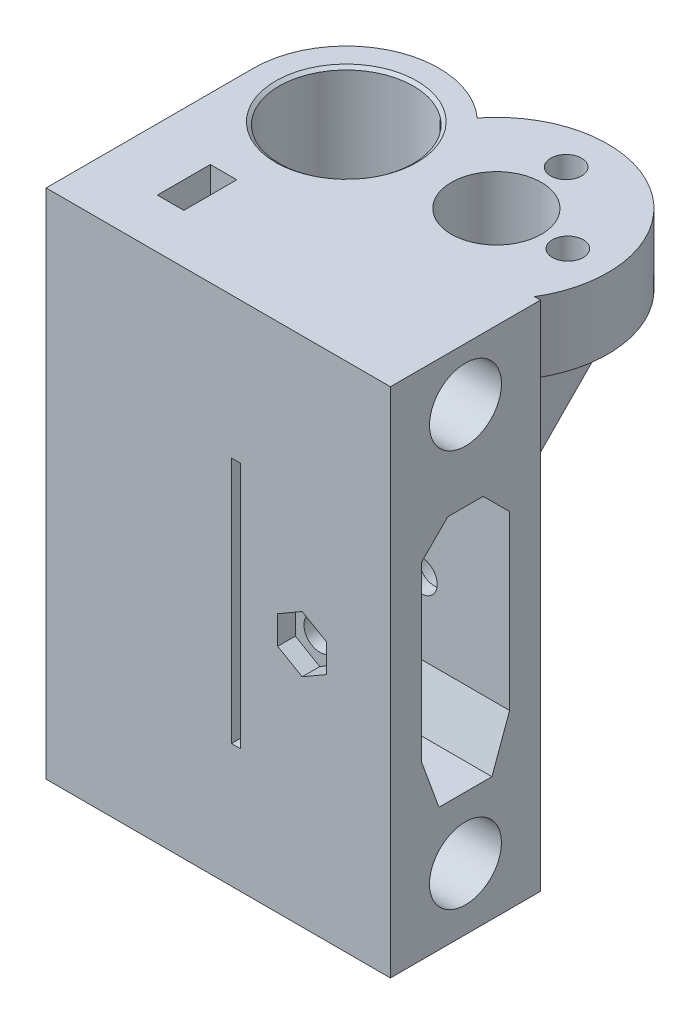
SolidWorks part; units mm, degrees
ref_plane "Front Plane" through (0, 0, 0) normal (0, 0, 1) x (1, 0, 0)
ref_plane "Top Plane" through (0, 0, 0) normal (0, 1, 0) x (1, 0, 0)
ref_plane "Right Plane" through (0, 0, 0) normal (1, 0, 0) x (0, 0, -1)
sketch "Sketch1" plane through (0, 0, 0) normal (0, 0, 1) x (1, 0, 0)
  line L1 (-40.75, -31) -> (40.75, -31)
  line L2 (-40.75, -31) -> (-40.75, 31)
  line L3 (-40.75, 31) -> (40.75, 31)
  line L4 (40.75, -31) -> (40.75, 31)
  line L5 (-40.75, -31) -> (40.75, 31) construction
  line L6 (-40.75, 31) -> (40.75, -31) construction
  point P0 (0, 0)
  dimension "D1" = 81.5
  dimension "D2" = 62
extrude "Boss-Extrude1" add sketch "Sketch1" along normal blind 17
sketch "Sketch2" plane through (0, 0, 17) normal (0, 0, 1) x (1, 0, 0)
  line L0 (22.55, -31) -> (22.55, -27)
  line L1 (-40.75, -31) -> (40.75, -31) construction
  line L2 (22.55, -27) -> (1.75, -27)
  line L3 (1.75, -27) -> (1.75, -22)
  line L4 (1.75, -22) -> (-10.75, -22)
  line L5 (-10.75, -22) -> (-10.75, 11.75)
  line L6 (-10.75, 11.75) -> (-40.75, 11.75)
  line L7 (-40.75, 31) -> (-40.75, -31) construction
  line L8 (-40.75, 11.75) -> (-40.75, -31)
  line L9 (-40.75, -31) -> (22.55, -31)
  line L10 (40.75, -31) -> (40.75, 31) construction
  line L11 (40.75, 31) -> (-40.75, 31) construction
  dimension "D1" = 18.2
  dimension "D2" = 4
  dimension "D3" = 20.8
  dimension "D4" = 5
  dimension "D5" = 12.5
  dimension "D6" = 19.25
extrude "Cut-Extrude2" cut sketch "Sketch2" against normal through all
chamfer "Chamfer2" distance 11 angle 45 1 edges at (-40.75, 31, 8.5)
sketch "Sketch3" plane through (0, 0, 0) normal (0, 0, -1) x (-1, 0, 0)
  line L0 (-40.75, 31) -> (29.75, 31) construction
  line L1 (35.25, -14.75) -> (4.25, -14.75) construction
  line L2 (35.25, -14.75) -> (35.25, 16.25) construction
  line L3 (35.25, 16.25) -> (4.25, 16.25) construction
  line L4 (4.25, -14.75) -> (4.25, 16.25) construction
  line L5 (35.25, -14.75) -> (4.25, 16.25) construction
  line L6 (35.25, 16.25) -> (4.25, -14.75) construction
  line L7 (-40.75, -31) -> (-40.75, 31) construction
  circle A0 centre (35.25, 16.25) radius 1.8
  circle A1 centre (4.25, 16.25) radius 1.8
  circle A2 centre (4.25, -14.75) radius 1.8
  point P0 (19.75, 0.75)
  dimension "D4" = 3.6
  dimension "D1" = 31
  dimension "D2" = 30.25
  dimension "D3" = 60.5
extrude "Cut-Extrude3" cut sketch "Sketch3" against normal through all
sketch "Sketch4" plane through (0, 0, 17) normal (0, 0, 1) x (1, 0, 0)
  circle A0 centre (-4.25, -14.75) radius 3.1
  circle A1 centre (-4.25, 16.25) radius 3.1
  circle A2 centre (-35.25, 16.25) radius 3.1
  dimension "D1" = 6.2
extrude "Cut-Extrude4" cut sketch "Sketch4" against normal blind 3.5
sketch "Sketch5" plane through (0, 0, 0) normal (0, 0, -1) x (-1, 0, 0)
  line L0 (28.2406, 15.75) -> (11.2341, 15.75)
  line L1 (11.2341, 15.75) -> (2.7182, 1)
  line L2 (2.7182, 1) -> (10.75, -12.9115)
  line L3 (10.75, -22) -> (10.75, 11.75) construction
  line L4 (35.25, -14.75) -> (4.25, -14.75) construction
  line L5 (35.25, -14.75) -> (35.25, 16.25) construction
  line L6 (35.25, 16.25) -> (4.25, 16.25) construction
  line L7 (4.25, -14.75) -> (4.25, 16.25) construction
  line L8 (35.25, -14.75) -> (4.25, 16.25) construction
  line L9 (35.25, 16.25) -> (4.25, -14.75) construction
  line L10 (28.2406, 15.75) -> (30.55, 11.75)
  line L11 (10.75, 11.75) -> (40.75, 11.75) construction
  line L12 (10.75, -12.9115) -> (30.55, 11.75)
  circle A0 centre (19.75, 1) radius 14.75 construction
  point P6 (19.75, 0.75)
  dimension "D4" = 29.5
  dimension "D1" = 120
  dimension "D2" = 120
  dimension "D3" = 0.25
  dimension "D5" = 120
  dimension "D6" = 10.2
extrude "Cut-Extrude5" cut sketch "Sketch5" against normal through all
fillet "Fillet1" radius 2 1 edges at (-28.2406, 15.75, 8.5)
fillet "Fillet2" radius 3 1 edges at (-11.2341, 15.75, 8.5)
fillet "Fillet3" radius 3.5 1 edges at (-2.7182, 1, 8.5)
sketch "Sketch8" plane through (0, 31, 0) normal (0, 1, 0) x (1, 0, 0)
  line L0 (-40.75, -17) -> (-40.75, 0) construction
  line L2 (40.75, -17) -> (-29.75, -17) construction
  circle A0 centre (12.25, -23.5) radius 7.6
  circle A1 centre (12.25, -23.5) radius 10.5
  dimension "D1" = 15.2
  dimension "D4" = 21
  dimension "D2" = 53
  dimension "D3" = 6.5
extrude "Boss-Extrude2" add sketch "Sketch8" against normal blind 58
sketch "Sketch14" plane through (0, -27, 0) normal (0, -1, 0) x (1, 0, 0)
  line L0 (22.75, 23.5) -> (22.75, 17)
  line L1 (22.55, 17) -> (40.75, 17) construction
  line L2 (20.4962, 17) -> (22.75, 17)
  line L3 (12.25, 23.5) -> (12.25, -49976.5) construction
  line L4 (4.0038, 17) -> (1.75, 17)
  line L5 (1.75, 23.5) -> (1.75, 17)
  arc A0 (20.4962, 17) -> (4.0038, 17) centre (12.25, 23.5) ccw construction
  arc A1 (20.4962, 17) -> (22.75, 23.5) centre (12.25, 23.5) ccw
  arc A2 (4.0038, 17) -> (1.75, 23.5) centre (12.25, 23.5) cw
extrude "Boss-Extrude4" add sketch "Sketch14" against normal up to surface (58 mm away) up to face at (7.75, 31, 14.1667)
sketch "Sketch6" plane through (40.75, 0, 0) normal (1, 0, 0) x (0, 0, -1)
  line L1 (-10.5, 15) -> (-6.5, 15)
  line L2 (-6.5, 15) -> (-3.5, 12)
  line L3 (-3.5, 12) -> (-3.5, -7.505)
  line L4 (-3.5, -7.505) -> (-5.5, -13)
  line L5 (-5.5, -13) -> (-11.5, -13)
  line L6 (-11.5, -13) -> (-13.5, -7.505)
  line L8 (-13.5, -7.505) -> (-13.5, 12)
  line L9 (-13.5, 12) -> (-10.5, 15)
  line L10 (-17, 31) -> (0, 31) construction
  line L11 (0, -31) -> (0, 31) construction
  dimension "D1" = 45
  dimension "D2" = 160
  dimension "D3" = 160
  dimension "D4" = 28
  dimension "D5" = 10
  dimension "D6" = 16
  dimension "D7" = 3.5
  dimension "D8" = 3
  dimension "D9" = 2
extrude "Cut-Extrude6" cut sketch "Sketch6" against normal blind 41.5
sketch "Sketch7" plane through (-0.75, 0, 0) normal (1, 0, 0) x (0, 0, -1)
  line L0 (-3.5, -7.505) -> (-3.5, 12) construction
  line L1 (-13.5, 11.75) -> (-3.5, 11.75)
  line L2 (-13.5, 11.75) -> (-13.5, -10.25)
  line L3 (-13.5, -10.25) -> (-3.5, -10.25)
  line L4 (-3.5, 11.75) -> (-3.5, -10.25)
  line L5 (-13.5, 11.75) -> (-3.5, -10.25) construction
  line L6 (-13.5, -10.25) -> (-3.5, 11.75) construction
  line L7 (-13.5, 12) -> (-13.5, -7.505) construction
  line L8 (-17, 31) -> (0, 31) construction
  point P4 (-8.5, 0.75)
  dimension "D1" = 19.25
  dimension "D2" = 22
extrude "Cut-Extrude7" cut sketch "Sketch7" against normal up to next
sketch "Sketch10" plane through (0, 31, 0) normal (0, 1, 0) x (1, 0, 0)
  line L0 (1.75, -17) -> (-29.75, -17) construction
  line L1 (-40.75, -17) -> (-40.75, 0) construction
  circle A0 centre (29.25, -23.5) radius 7.15
  circle A1 centre (29.25, -23.5) radius 12.625
  dimension "D1" = 14.3
  dimension "D2" = 25.25
  dimension "D3" = 6.5
  dimension "D4" = 70
extrude "Boss-Extrude3" add sketch "Sketch10" against normal blind 8
sketch "Sketch9" plane through (0, 31, 0) normal (0, 1, 0) x (1, 0, 0)
  circle A0 centre (12.25, -23.5) radius 7.6
  arc A1 (8.3117, -17) -> (17.7609, -28.7336) centre (12.25, -23.5) ccw construction
extrude "Cut-Extrude8" cut sketch "Sketch9" against normal through all
sketch "Sketch11" plane through (0, 31, 0) normal (0, 1, 0) x (1, 0, 0)
  circle A0 centre (29.25, -23.5) radius 7.15
  arc A1 (22.489, -25.8264) -> (32.2287, -17) centre (29.25, -23.5) ccw construction
extrude "Cut-Extrude9" cut sketch "Sketch11" against normal up to vertex (8 mm away) up to point (19.3047, 23, 31.277)
sketch "Sketch12" plane through (0, 31, 0) normal (0, 1, 0) x (1, 0, 0)
  line L0 (22.5325, -16.7825) -> (29.25, -23.5) construction
  line L1 (29.25, -23.5) -> (35.9675, -30.2175) construction
  line L2 (29.25, -23.5) -> (12.25, -23.5) construction
  circle A0 centre (22.5325, -16.7825) radius 1.8
  circle A1 centre (35.9675, -30.2175) radius 1.8
  point P4 (29.25, -23.5)
  dimension "D1" = 3.6
  dimension "D2" = 9.5
  dimension "D3" = 45
extrude "Cut-Extrude10" cut sketch "Sketch12" against normal up to surface (8 mm away) up to face at (31.9801, 23, 27.1246)
ref_plane "Plane1" through (0, 25, 0) normal (0, -1, 0) x (-1, 0, 0)
sketch "Sketch13" plane through (0, 25, 0) normal (0, -1, 0) x (1, 0, 0)
  line L0 (35.9675, 30.2175) -> (29.25, 23.5) construction
  line L1 (33.5303, 32.6548) -> (32.6382, 29.3254)
  line L2 (32.6382, 29.3254) -> (35.0754, 26.8882)
  line L3 (35.0754, 26.8882) -> (38.4048, 27.7803)
  line L4 (38.4048, 27.7803) -> (39.2968, 31.1096)
  line L5 (39.2968, 31.1096) -> (36.8596, 33.5468)
  line L6 (36.8596, 33.5468) -> (33.5303, 32.6548)
  line L7 (24.9697, 19.2197) -> (21.6404, 20.1118) construction
  line L8 (21.6404, 20.1118) -> (19.2032, 17.6746)
  line L9 (19.2032, 17.6746) -> (20.0952, 14.3452)
  line L10 (20.0952, 14.3452) -> (23.4246, 13.4532)
  line L11 (23.4246, 13.4532) -> (25.8618, 15.8904)
  line L12 (25.8618, 15.8904) -> (24.9697, 19.2197) construction
  line L13 (29.25, 23.5) -> (22.5325, 16.7825) construction
  line L14 (21.6404, 20.1118) -> (22.75, 22.0337)
  line L15 (25.8618, 15.8904) -> (27.7837, 17)
  line L16 (27.7837, 17) -> (22.75, 22.0337)
  line L17 (22.55, 17) -> (40.75, 17) construction
  circle A0 centre (35.9675, 30.2175) radius 2.985 construction
  circle A1 centre (22.5325, 16.7825) radius 2.985 construction
  arc A2 (24.3193, 17) -> (22.75, 18.5693) centre (22.5325, 16.7825) ccw construction
  arc A3 (32.2287, 17) -> (22.489, 25.8264) centre (29.25, 23.5) ccw construction
  point P27 (33.8568, 28.1068)
  dimension "D1" = 5.97
  dimension "D2" = 165
  dimension "D3" = 165
extrude "Cut-Extrude11" cut sketch "Sketch13" along normal blind 3
ref_plane "Plane2" through (0, 21.5, 0) normal (0, 1, 0) x (1, 0, 0)
sketch "Sketch15" plane through (0, 21.5, 0) normal (0, 1, 0) x (1, 0, 0)
  line L0 (22.75, -17) -> (22.75, -20.9)
  line L1 (22.75, -20.9) -> (27.1119, -17)
  line L2 (27.1119, -17) -> (22.75, -17)
  line L3 (27.7837, -17) -> (22.75, -17) construction
  line L4 (22.75, -22.0337) -> (22.75, -17) construction
  dimension "D1" = 138.2
  dimension "D2" = 3.9
extrude "Boss-Extrude5" add sketch "Sketch15" against normal blind 1
sketch "Sketch17" plane through (0, 0, 17) normal (0, 0, 1) x (1, 0, 0)
  line L0 (39.55, 23) -> (39.55, 13.66)
  line L1 (32.2287, 23) -> (40.0732, 23) construction
  line L2 (40.75, -31) -> (40.75, 31) construction
  line L3 (39.55, 13.66) -> (35.41, 12.05)
  line L4 (35.41, 12.05) -> (35.41, 23)
  line L5 (39.55, 23) -> (35.41, 23)
  dimension "D1" = 1.2
  dimension "D2" = 9.34
  dimension "D3" = 10.95
  dimension "D4" = 4.14
sketch "Sketch18" plane through (0, 23, 0) normal (0, -1, 0) x (1, 0, 0)
  line L0 (39.55, 17) -> (41.1599, 23.0081)
  line L1 (32.2287, 17) -> (40.0732, 17) construction
  line L2 (41.1599, 23.0081) -> (37.3211, 24.1323)
  line L3 (37.3211, 24.1323) -> (35.41, 17)
  line L4 (39.55, 17) -> (35.41, 17)
  dimension "D1" = 75
  dimension "D2" = 4
  dimension "D3" = 6.22
loft "Loft1" add profiles "Sketch18", "Sketch17" connector at (39.55, 23, 17) connector at (39.55, 23, 17)
sketch "Sketch19" plane through (0, 23, 0) normal (0, -1, 0) x (1, 0, 0)
  line L0 (27.46, 31.82) -> (22.0468, 27.2778)
  line L1 (22.55, 17) -> (40.75, 17) construction
  arc A0 (22.75, 23.5) -> (1.75, 23.5) centre (12.25, 23.5) ccw construction
  point P0 (27.46, 31.82)
  dimension "D1" = 13.29
  dimension "D2" = 14.82
  dimension "D3" = 40
ref_plane "Plane3" through (-4.3225, 0, 5.1513) normal (0.6428, 0, -0.766) x (-0.766, 0, -0.6428)
sketch "Sketch20" plane through (-4.3225, 0, 5.1513) normal (0.6428, 0, -0.766) x (-0.766, 0, -0.6428)
  line L0 (-34.4227, 23) -> (-34.4227, 12.35)
  line L1 (-34.4227, 12.35) -> (-41.4891, 23)
  line L2 (-41.4891, 23) -> (-34.4227, 23)
  dimension "D1" = 10.65
extrude "Boss-Extrude6" add sketch "Sketch20" against normal blind 4
sketch "Sketch21" plane through (40.75, 0, 0) normal (1, 0, 0) x (0, 0, -1)
  line L0 (-17, -31) -> (0, -31) construction
  line L1 (0, -31) -> (0, 31) construction
  circle A0 centre (-8.5, 25) radius 4.075
  circle A1 centre (-8.5, -20) radius 4.075
  dimension "D1" = 8.15
  dimension "D2" = 11
  dimension "D3" = 45
  dimension "D4" = 8.5
extrude "Cut-Extrude12" cut sketch "Sketch21" against normal blind 27.5 contours A0 region at (40.75, 25, 8.5)
extrude "Cut-Extrude13" cut sketch "Sketch21<3>" against normal blind 27.5 contours A1 region at (40.75, -20, 8.5)
sketch "Sketch21<3>" plane through (40.75, 0, 0) normal (1, 0, 0) x (0, 0, -1) same geometry as "Sketch21"
sketch "Sketch22" plane through (13.25, 0, 0) normal (1, 0, 0) x (0, 0, -1)
  circle A0 centre (-8.5, 25) radius 5
  circle A1 centre (-8.5, -20) radius 5
  dimension "D1" = 10
extrude "Cut-Extrude14" cut sketch "Sketch22" along normal blind 7.9
sketch "Sketch23" plane through (0, -27, 0) normal (0, -1, 0) x (1, 0, 0)
  line L0 (19.3047, 31.277) -> (17.4578, 29.0352)
  line L1 (19.3047, 31.277) -> (18.5329, 31.9128) construction
  line L2 (17.4578, 29.0352) -> (16.686, 29.671)
  line L3 (18.5329, 31.9128) -> (16.686, 29.671)
  line L4 (19.3047, 31.277) -> (16.686, 29.671) construction
  line L5 (17.4578, 29.0352) -> (18.5329, 31.9128) construction
  circle A0 centre (12.25, 23.5) radius 7.6 construction
  arc A1 (22.75, 23.5) -> (1.75, 23.5) centre (12.25, 23.5) ccw construction
  arc A2 (18.5329, 31.9128) -> (19.3047, 31.277) centre (12.25, 23.5) cw
  point P6 (17.9954, 30.474)
  dimension "D1" = 1
extrude "Cut-Extrude15" cut sketch "Sketch23" against normal offset from surface (57.5 mm away) 0.5 up to face at (35.9675, 31, 32.0175)
sketch "Sketch24" plane through (0, 0, 17) normal (0, 0, 1) x (1, 0, 0)
  line L0 (22.75, 20.5) -> (22.75, -27) construction
  line L1 (22.75, 15) -> (23.75, 15)
  line L2 (22.75, 15) -> (22.75, -13)
  line L3 (22.75, -13) -> (23.75, -13)
  line L4 (23.75, 15) -> (23.75, -13)
  line L5 (22.75, 15) -> (23.75, -13) construction
  line L6 (22.75, -13) -> (23.75, 15) construction
  line L7 (27.1119, 20.5) -> (22.75, 20.5) construction
  point P4 (23.25, 1)
  dimension "D1" = 1
  dimension "D2" = 5.5
  dimension "D3" = 28
extrude "Cut-Extrude16" cut sketch "Sketch24" against normal through all
chamfer "Chamfer4" distance 0.4 distance2 0.3 2 edges at (12.25, 31, 31.1) (29.25, 31, 30.65) first distance on face at (35.9675, 31, 32.0175)
ref_plane "Plane4" through (0, 0, 0) normal (0, 0, -1) x (-1, 0, 0)
mirror "Mirror1" about plane through (0, 0, 0) normal (0, 0, -1) of bodies 123 124
sketch "Sketch26" plane through (0, 0, 0) normal (0, 0, -1) x (-1, 0, 0)
  line L0 (-22.55, -31) -> (-40.75, -31) construction
  line L1 (-41.875, 31) -> (40.75, 31)
  line L2 (-41.875, 31) -> (-41.875, -31)
  line L3 (-41.875, -31) -> (40.75, -31)
  line L4 (40.75, 31) -> (40.75, -31)
  line L5 (-41.875, 31) -> (40.75, -31) construction
  line L6 (-41.875, -31) -> (40.75, 31) construction
  line L7 (40.75, 20) -> (40.75, 11.75) construction
  point P4 (-0.5625, 0)
extrude "Cut-Extrude18" cut sketch "Sketch26" against normal through all
sketch "Sketch27" plane through (1.75, 0, 0) normal (-1, 0, 0) x (0, 0, 1)
  line L1 (0, 31) -> (-17, 31)
  line L2 (0, 31) -> (0, -31)
  line L3 (0, -31) -> (-17, -31)
  line L4 (-17, 31) -> (-17, -31)
  line L5 (0, 31) -> (-17, -31) construction
  line L6 (0, -31) -> (-17, 31) construction
  point P4 (-8.5, 0)
extrude "Cut-Extrude19" cut sketch "Sketch27" along normal through all
sketch "Sketch28" plane through (0, 0, 0) normal (0, 0, 1) x (1, 0, 0)
  line L0 (40.75, 31) -> (40.75, -31) construction
  line L1 (1.75, 31) -> (40.75, 31) construction
  circle A0 centre (30.75, 0.75) radius 1.8
  point P3 (30.75, 0.75)
  dimension "D1" = 3.6
  dimension "D2" = 10
  dimension "D3" = 30.25
extrude "Cut-Extrude20" cut sketch "Sketch28" against normal through all
sketch "Sketch29" plane through (0, 0, -17) normal (0, 0, -1) x (-1, 0, 0)
  circle A0 centre (-30.75, 0.75) radius 3.1
  dimension "D1" = 6.2
extrude "Cut-Extrude21" cut sketch "Sketch29" against normal blind 2
sketch "Sketch30" plane through (0, 0, 0) normal (0, 0, 1) x (1, 0, 0)
  line L1 (30.75, 3.9485) -> (27.98, 2.3493)
  line L2 (27.98, 2.3493) -> (27.98, -0.8493)
  line L3 (27.98, -0.8493) -> (30.75, -2.4485)
  line L4 (30.75, -2.4485) -> (33.52, -0.8493)
  line L5 (33.52, -0.8493) -> (33.52, 2.3493)
  line L6 (33.52, 2.3493) -> (30.75, 3.9485)
  circle A0 centre (30.75, 0.75) radius 2.77 construction
  dimension "D1" = 5.54
extrude "Cut-Extrude22" cut sketch "Sketch30" against normal blind 2
sketch "Sketch31" plane through (1.75, 0, 0) normal (-1, 0, 0) x (0, 0, 1)
  circle A0 centre (-8.5, 25) radius 1.7
  circle A1 centre (-8.5, -20) radius 1.7
  circle A2 centre (-8.5, 25) radius 4.075 construction
  circle A3 centre (-8.5, -20) radius 4.075 construction
  dimension "D1" = 3.4
extrude "Cut-Extrude23" cut sketch "Sketch31" against normal through all
sketch "Sketch32" plane through (1.75, 0, 0) normal (-1, 0, 0) x (0, 0, 1)
  circle A0 centre (-8.5, 25) radius 3
  circle A1 centre (-8.5, -20) radius 3
  dimension "D1" = 6
extrude "Cut-Extrude24" cut sketch "Sketch32" against normal blind 3
ref_plane "Plane5" through (8.75, 0, 0) normal (-1, 0, 0) x (0, 0, 1)
sketch "Sketch33" plane through (8.75, 0, 0) normal (-1, 0, 0) x (0, 0, 1)
  line L0 (0, 31) -> (-23.5, 31) construction
  line L1 (-11.6, 31) -> (-5.6, 31)
  line L2 (-11.6, 31) -> (-11.6, 20.4)
  line L3 (-11.6, 20.4) -> (-5.6, 20.4)
  line L4 (-5.6, 31) -> (-5.6, 20.4)
  line L5 (-11.6, 31) -> (-5.6, 20.4) construction
  line L6 (-11.6, 20.4) -> (-5.6, 31) construction
  line L7 (0, -27) -> (0, 31) construction
  line L8 (-23.5, -27) -> (0, -27) construction
  line L9 (-5.6, -27) -> (-11.6, -27)
  line L10 (-5.6, -27) -> (-5.6, -16.4)
  line L11 (-5.6, -16.4) -> (-11.6, -16.4)
  line L12 (-11.6, -27) -> (-11.6, -16.4)
  line L13 (-5.6, -27) -> (-11.6, -16.4) construction
  line L14 (-5.6, -16.4) -> (-11.6, -27) construction
  point P4 (-8.6, 25.7)
  point P13 (-8.6, -21.7)
  dimension "D1" = 5.6
  dimension "D2" = 6
  dimension "D3" = 10.6
  dimension "D4" = 5.6
  dimension "D5" = 6
  dimension "D6" = 10.6
extrude "Cut-Extrude25" cut sketch "Sketch33" against normal blind 3
sketch "Sketch34" plane through (22.55, 0, 0) normal (-1, 0, 0) x (0, 0, 1)
  line L1 (0, -31) -> (-17, -31)
  line L2 (0, -31) -> (0, -27)
  line L3 (0, -27) -> (-17, -27)
  line L4 (-17, -31) -> (-17, -27)
  line L5 (0, -31) -> (-17, -27) construction
  line L6 (0, -27) -> (-17, -31) construction
  point P4 (-8.5, -29)
extrude "Cut-Extrude26" cut sketch "Sketch34" against normal through all
ref_plane "Plane6" through (0, 31, 0) normal (0, 1, 0) x (1, 0, 0)
sketch "Sketch35" plane through (0, 31, 0) normal (0, 1, 0) x (1, 0, 0)
  line L2 (20.6861, 32.761) -> (20.6861, 14.2237)
  arc A1 (20.6861, 14.2237) -> (20.6861, 32.761) centre (29.2423, 23.4923) ccw
extrude "Boss-Extrude7" add sketch "Sketch35" against normal up to surface (8 mm away) up to face at (32.5774, 23, -27.234)
sketch "Sketch36" plane through (0, 31, 0) normal (0, 1, 0) x (1, 0, 0)
  line L0 (29.25, 30.65) -> (29.25, 16.35) construction
  line L1 (22.1, 23.5) -> (36.4, 23.5) construction
  circle A0 centre (29.25, 23.5) radius 5.1
  dimension "D1" = 10.2
extrude "Cut-Extrude27" cut sketch "Sketch36" against normal blind 10
sketch "Sketch37" plane through (0, 31, 0) normal (0, 1, 0) x (1, 0, 0)
  circle A0 centre (29.1561, 31.4995) radius 1.75
  circle A1 centre (29.25, 23.5) radius 8 construction
  circle A2 centre (37.2495, 23.5939) radius 1.75
  circle A3 centre (29.25, 23.5) radius 8 construction
  circle A8 centre (29.3439, 15.5006) radius 1.75 [skipped]
  circle A9 centre (29.25, 23.5) radius 8 construction
  circle A10 centre (21.2506, 23.4061) radius 1.75 [skipped]
  circle A11 centre (29.25, 23.5) radius 8 construction
  point P18 (29.25, 23.5)
  dimension "D1" = 3.5
  dimension "D3" = 16
  dimension "D2" = 4
extrude "Cut-Extrude28" cut sketch "Sketch37" against normal blind 10
sketch "Sketch38" plane through (0, 23, 0) normal (0, -1, 0) x (1, 0, 0)
  circle A0 centre (29.1561, -31.4995) radius 3.3206
  circle A1 centre (37.2495, -23.5939) radius 3.2422
extrude "Cut-Extrude29" cut sketch "Sketch38" along normal blind 10
